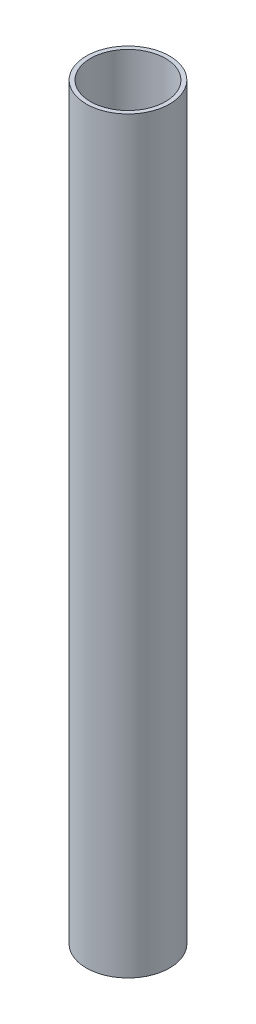
SolidWorks part; units mm, degrees
material "Toray T700"
ref_plane "Front" through (0, 0, 0) normal (0, 0, 1) x (1, 0, 0)
ref_plane "Top" through (0, 0, 0) normal (0, 1, 0) x (1, 0, 0)
ref_plane "Right" through (0, 0, 0) normal (1, 0, 0) x (0, 0, -1)
sketch "Sketch1" plane through (0, 0, 0) normal (0, 1, 0) x (1, 0, 0)
  line L5 (4.7969, 0) -> (-5.97, 0) construction
  circle A0 centre (0, 0) radius 10
  circle A1 centre (0, 0) radius 9
  dimension "D1" = 20
  dimension "D2" = 18
extrude "Boss-Extrude1" add sketch "Sketch1" along normal blind 179.7
ref_axis "Axis1" through (0, 179.7, 0) along (0, -1, 0)
